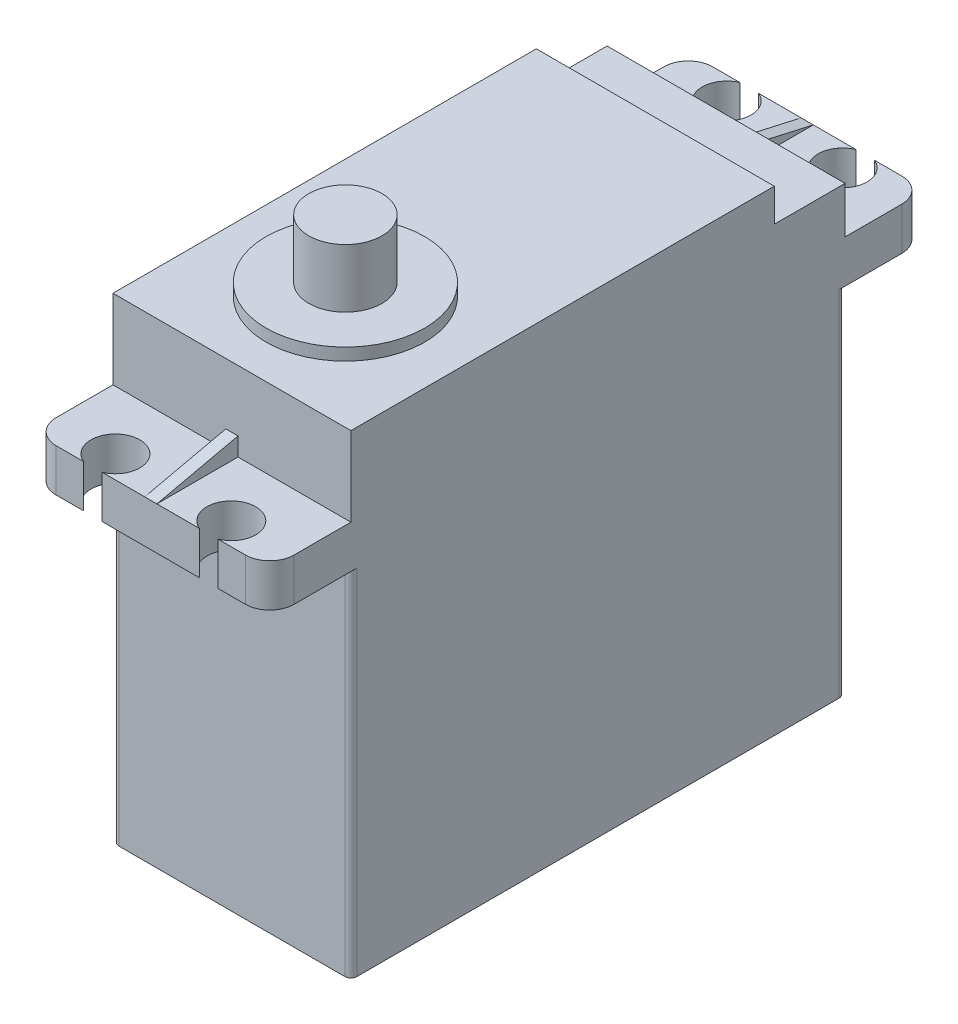
SolidWorks part; units mm, degrees
ref_plane "Front Plane" through (0, 0, 0) normal (0, 0, 1) x (1, 0, 0)
ref_plane "Top Plane" through (0, 0, 0) normal (0, 1, 0) x (1, 0, 0)
ref_plane "Right Plane" through (0, 0, 0) normal (1, 0, 0) x (0, 0, -1)
sketch "Sketch1" plane through (0, 0, 0) normal (1, 0, 0) x (0, 0, -1)
  line L0 (-40.5, 0) -> (0, 0)
  line L1 (0, 0) -> (0, 29)
  line L2 (0, 32.5) -> (6.65, 32.5)
  line L3 (6.65, 32.5) -> (6.65, 29)
  line L4 (6.65, 29) -> (0, 29)
  line L5 (0, 32.5) -> (0, 36.3)
  line L6 (0, 36.3) -> (-5.8, 36.3)
  line L7 (-5.8, 36.3) -> (-5.8, 39)
  line L8 (-5.8, 39) -> (-40.5, 39)
  line L9 (-40.5, 39) -> (-40.5, 32.5)
  line L10 (-40.5, 32.5) -> (-47.15, 32.5)
  line L11 (-47.15, 32.5) -> (-47.15, 29)
  line L12 (-47.15, 29) -> (-40.5, 29)
  line L13 (-40.5, 29) -> (-40.5, 0)
  point P15 (0, 0)
  point P16 (0, 0)
  point P17 (6.48, 30.6663)
  dimension "D1" = 40.5
  dimension "D2" = 29
  dimension "D3" = 53.8
  dimension "D4" = 36.3
  dimension "D5" = 5.8
  dimension "D6" = 39
  dimension "D9" = 3.5
extrude "Main" add sketch "Sketch1" along normal mid plane 19.5
sketch "Sketch4" plane through (0, 39, 0) normal (0, 1, 0) x (1, 0, 0)
  line L0 (9.75, -40.5) -> (-9.75, -40.5) construction
  line L1 (9.75, -40.5) -> (-9.75, -40.5) construction
  circle A0 centre (0, -31.2) radius 6.5
  point P4 (0, -40.5)
  point P5 (0, 0)
  dimension "D2" = 13
  dimension "D1" = 9.3
extrude "BaseCircle" add sketch "Sketch4" along normal blind 1
sketch "Sketch5" plane through (0, 40, 0) normal (0, 1, 0) x (1, 0, 0)
  circle A1 centre (0, -31.2) radius 3
  dimension "D1" = 6
extrude "Gear" add sketch "Sketch5" along normal blind 4.8
sketch "Sketch9" plane through (0, 32.5, 0) normal (0, 1, 0) x (-1, 0, 0)
  line L0 (-9.75, 40.5) -> (9.75, 40.5) construction
  line L1 (-9.75, 0) -> (9.75, 0) construction
  line L2 (-9.75, -6.65) -> (-9.75, 0) construction
  line L3 (9.75, -6.65) -> (9.75, 0) construction
  circle A0 centre (-4.75, 45.3) radius 2
  circle A1 centre (4.75, 45.3) radius 2
  circle A2 centre (4.75, -4.8) radius 2
  circle A3 centre (-4.75, -4.8) radius 2
  point P12 (0, 0)
  point P17 (0, 0)
  point P18 (0, 0)
  point P19 (0, 0)
  dimension "D6" = 4
  dimension "D9" = 5
  dimension "D1" = 4.8
  dimension "D7" = 4.8
  dimension "D10" = 5
  dimension "D11" = 9.5
extrude "Fixing-Hole" cut sketch "Sketch9" against normal blind 19.05
fillet "FixingFillet" radius 2 4 edges at (9.75, 30.75, -6.65) (-9.75, 30.75, -6.65) (-9.75, 30.75, 47.15) (9.75, 30.75, 47.15)
sketch "Esquisse1" plane through (0, 0, 0) normal (1, 0, 0) x (0, 0, -1)
  line L0 (6.65, 32.5) -> (0, 34)
  line L1 (0, 34) -> (0, 32.5)
  line L2 (0, 32.5) -> (6.65, 32.5)
  line L3 (-47.15, 32.5) -> (-40.5, 32.5)
  line L4 (-40.5, 32.5) -> (-40.5, 34)
  line L5 (-40.5, 39) -> (-40.5, 32.5) construction
  line L6 (-40.5, 34) -> (-47.15, 32.5)
  point P2 (0, 0)
  dimension "D1" = 1.5
extrude "Reinforcement" add sketch "Esquisse1" along normal mid plane 1
fillet "ServoFillet" radius 0.5 4 edges at (9.75, 14.5, 40.5) (-9.75, 14.5, 40.5) (9.75, 14.5, 0) (-9.75, 14.5, 0)
